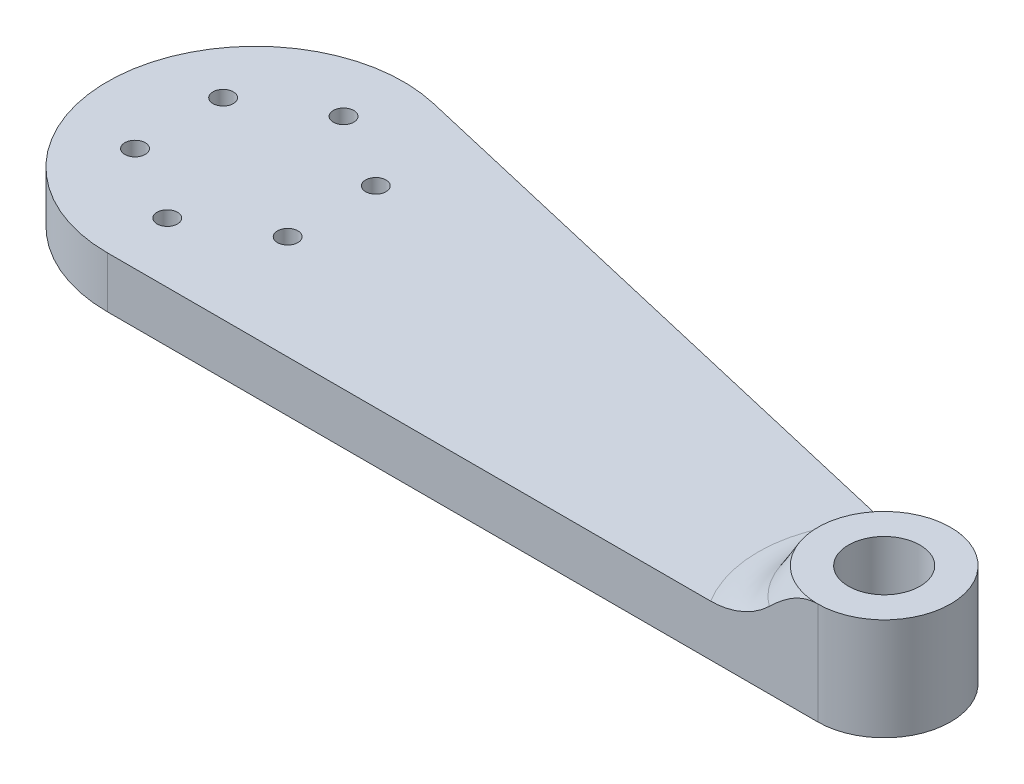
SolidWorks part; units mm, degrees
ref_plane "前视基准面" through (0, 0, 0) normal (0, 0, 1) x (1, 0, 0)
ref_plane "上视基准面" through (0, 0, 0) normal (0, 1, 0) x (1, 0, 0)
ref_plane "右视基准面" through (0, 0, 0) normal (1, 0, 0) x (0, 0, -1)
sketch "草图1" plane through (0, 0, 0) normal (0, 1, 0) x (1, 0, 0)
  line L0 (0, 0) -> (0, -84.4118) construction
  line L1 (0, 0) -> (115.9996, 0) construction
  line L4 (0, -29) -> (139.0827, -29)
  line L7 (6.5851, 28.2424) -> (142.0347, -3.3396)
  circle A0 centre (0, 0) radius 17.25 construction
  arc A2 (139.0827, -29) -> (142.0347, -3.3396) centre (139.0827, -16) ccw
  circle A3 centre (139.0827, -16) radius 7
  arc A5 (0, 29) -> (0, -29) centre (0, 0) ccw
  circle A6 centre (0, 0) radius 29 construction
  arc A7 (0, 29) -> (6.5851, 28.2424) centre (0, 0) cw
  circle A8 centre (139.0827, -16) radius 13
  circle A9 centre (0, -17.25) radius 2
  circle A10 centre (-14.9389, -8.625) radius 2
  circle A11 centre (-14.9389, 8.625) radius 2
  circle A12 centre (0, 17.25) radius 2
  circle A13 centre (14.9389, 8.625) radius 2
  circle A14 centre (14.9389, -8.625) radius 2
  point P7 (-21.2419, -15.2737)
  point P10 (0, 0)
  point P34 (0, 0)
  dimension "D1" = 34.5
  dimension "D4" = 14
  dimension "D6" = 6
  dimension "D7" = 58
  dimension "D8" = 4
  dimension "D5" = 140
  dimension "D9" = 6
extrude "凸台-拉伸2" add sketch "草图1" along normal blind 20 contours A2 A8 A3 region at (126.5332, 0, 14.5563)
extrude "凸台-拉伸3" add sketch "草图1<3>" along normal blind 10 contours A8 L7 A7 A5 L4 region at (44.6068, 0, 5.1315)
sketch "草图1<3>" plane through (0, 0, 0) normal (0, 1, 0) x (1, 0, 0) same geometry as "草图1"
chamfer "倒角2" distance 10 angle 31 1 edges at (126.1679, 10, 14.5143) first distance on face at (139.0827, 20, 29)
fillet "圆角1" radius 10 1 edges at (120.1986, 10, 13.8276)
